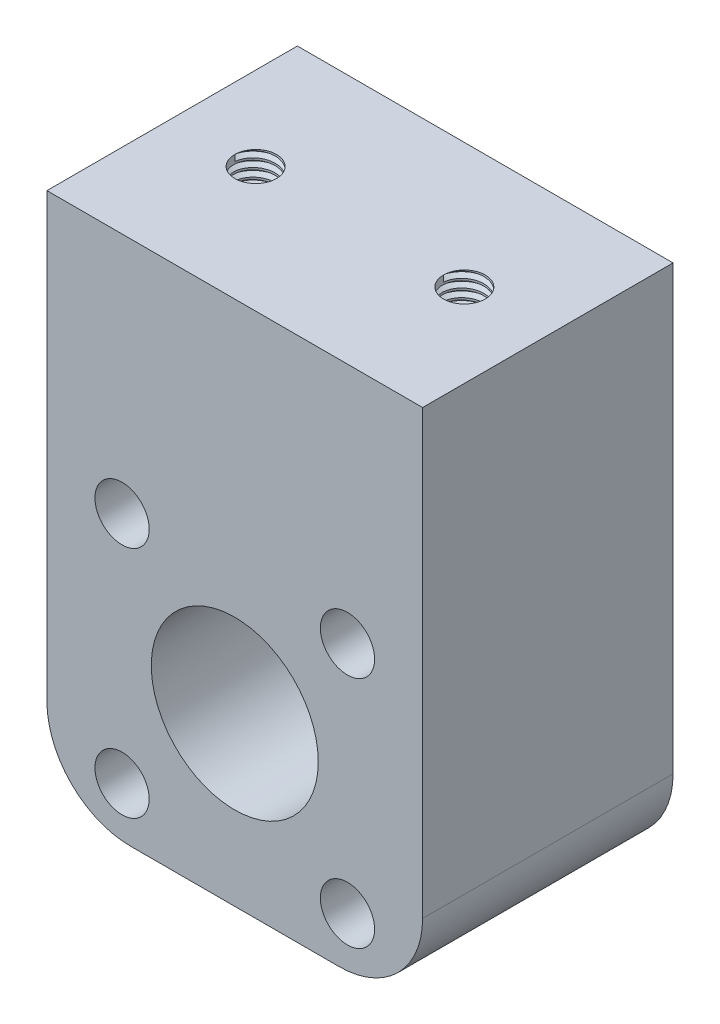
SolidWorks part; units mm, degrees
material "1.0037 (S235JR)"
ref_plane "Front Plane" through (0, 0, 0) normal (0, 0, 1) x (1, 0, 0)
ref_plane "Top Plane" through (0, 0, 0) normal (0, 1, 0) x (1, 0, 0)
ref_plane "Right Plane" through (0, 0, 0) normal (1, 0, 0) x (0, 0, -1)
sketch "Sketch1" plane through (0, 0, 0) normal (0, 0, 1) x (1, 0, 0)
  line L1 (-22.5, 31.5) -> (22.5, 31.5)
  line L2 (-22.5, 31.5) -> (-22.5, -31.5)
  line L3 (-22.5, -31.5) -> (22.5, -31.5)
  line L4 (22.5, 31.5) -> (22.5, -31.5)
  line L5 (-22.5, 31.5) -> (22.5, -31.5) construction
  line L6 (-22.5, -31.5) -> (22.5, 31.5) construction
  point P0 (0, 0)
  dimension "D1" = 63
  dimension "D2" = 45
extrude "Boss-Extrude1" add sketch "Sketch1" along normal blind 30
sketch "Sketch2" plane through (0, 0, 30) normal (0, 0, 1) x (1, 0, 0)
  line L0 (-22.5, -31.5) -> (22.5, -31.5) construction
  circle A0 centre (0, -11.5) radius 10
  dimension "D2" = 20
  dimension "D1" = 20
extrude "Cut-Extrude1" cut sketch "Sketch2" against normal through all
sketch "Sketch3" plane through (0, 0, 30) normal (0, 0, 1) x (1, 0, 0)
  line L0 (-22.5, -31.5) -> (22.5, -31.5) construction
  circle A0 centre (-13.5, -25.5) radius 3.25
  circle A1 centre (13.5, -25.5) radius 3.25
  circle A2 centre (13.5, 2.5) radius 3.25
  circle A3 centre (-13.5, 2.5) radius 3.25
  dimension "D5" = 6.5
  dimension "D1" = 13.5
  dimension "D2" = 13.5
  dimension "D3" = 6
  dimension "D4" = 6
  dimension "D6" = 28
  dimension "D7" = 28
extrude "Cut-Extrude2" cut sketch "Sketch3" against normal through all
fillet "Fillet1" radius 10 2 edges at (-22.5, -31.5, 15) (22.5, -31.5, 15)
sketch "Sketch4" plane through (0, 31.5, 0) normal (0, 1, 0) x (1, 0, 0)
  line L0 (22.5, 0) -> (-22.5, 0) construction
  line L1 (-22.5, -30) -> (-22.5, 0) construction
  line L2 (22.5, -30) -> (22.5, 0) construction
  circle A0 centre (-12.5, -15) radius 2.5
  circle A1 centre (12.5, -15) radius 2.5
  dimension "D1" = 5
  dimension "D2" = 5
  dimension "D3" = 15
  dimension "D4" = 15
  dimension "D5" = 10
  dimension "D6" = 10
extrude "Cut-Extrude3" cut sketch "Sketch4" against normal blind 10
thread "Thread1" pitch 1 method cut profile "Thread Profile1" start angle 0, offset 0, length 10, pitch 1, diameter 5
ref_plane "Plane1" through (10, 31.5, 15) normal (0, 0, 1) x (-1, 0, 0)
sketch "Thread Profile1" plane through (10, 31.5, 15) normal (0, 0, 1) x (-1, 0, 0)
  line L0 (0, 0) -> (0, 1) construction
  line L1 (0, 0) -> (0.5413, 0.3125)
  line L2 (0.5413, 0.3125) -> (0.5413, 0.4375)
  line L3 (0.5413, 0.4375) -> (0, 0.75)
  line L4 (0.5413, 0.375) -> (0, 0.375) construction
  line L11 (0, 0) -> (0, 0.75)
  point P2 (0, 0)
  dimension "Pitch" = 1
  dimension "Profile_Angle" = 60
  dimension "Profile_Land" = 0.125
  dimension "Profile_Height" = 0.5413
thread "Thread2" pitch 1 method cut profile "Thread Profile2" start angle 0, offset 0, length 10, pitch 1, diameter 5
ref_plane "Plane2" through (-15, 31.5, 15) normal (0, 0, 1) x (-1, 0, 0)
sketch "Thread Profile2" plane through (-15, 31.5, 15) normal (0, 0, 1) x (-1, 0, 0)
  line L0 (0, 0) -> (0, 1) construction
  line L1 (0, 0) -> (0.5413, 0.3125)
  line L2 (0.5413, 0.3125) -> (0.5413, 0.4375)
  line L3 (0.5413, 0.4375) -> (0, 0.75)
  line L4 (0.5413, 0.375) -> (0, 0.375) construction
  line L11 (0, 0) -> (0, 0.75)
  point P2 (0, 0)
  dimension "Pitch" = 1
  dimension "Profile_Angle" = 60
  dimension "Profile_Land" = 0.125
  dimension "Profile_Height" = 0.5413
